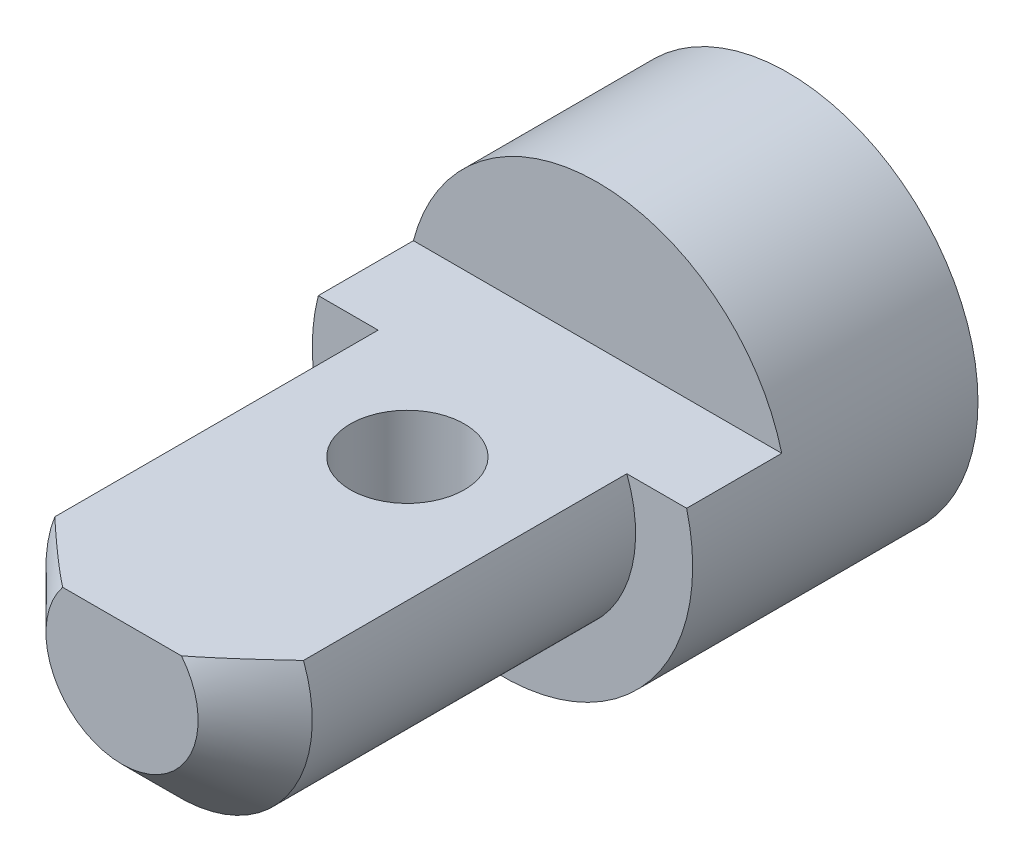
SolidWorks part; units mm, degrees
ref_plane "Front Plane" through (0, 0, 0) normal (0, 0, 1) x (1, 0, 0)
ref_plane "Top Plane" through (0, 0, 0) normal (0, 1, 0) x (1, 0, 0)
ref_plane "Right Plane" through (0, 0, 0) normal (1, 0, 0) x (0, 0, -1)
sketch "Sketch1" plane through (0, 0, 0) normal (0, 0, 1) x (1, 0, 0)
  line L0 (-19.3649, 5) -> (19.3649, 5)
  circle A0 centre (0, 0) radius 20
  circle A1 centre (0, 0) radius 14
  dimension "D1" = 40
  dimension "D2" = 28
  dimension "D3" = 5
extrude "Boss-Extrude1" add sketch "Sketch1" against normal blind 20 contours L0 A1 | L0 A1 | A1 L0 A0 | A1 L0 A0 region at (0, 19.5847, 0) region at (-16.2208, 4.5283, 0) region at (0, 8.7223, 0) region at (0, -3.3512, 0)
extrude "Boss-Extrude2" add sketch "Sketch1<4>" along normal blind 10 contours A1 L0 A0 region at (-16.2208, 4.5283, 0)
sketch "Sketch1<4>" plane through (0, 0, 0) normal (0, 0, 1) x (1, 0, 0) same geometry as "Sketch1"
extrude "Boss-Extrude3" add sketch "Sketch1<5>" along normal blind 50 contours L0 A1 region at (0, -3.3512, 0)
sketch "Sketch1<5>" plane through (0, 0, 0) normal (0, 0, 1) x (1, 0, 0) same geometry as "Sketch1"
chamfer "Chamfer3" distance 6 angle 45 1 edges at (0, -14, 50)
sketch "Sketch3" plane through (0, 5, 0) normal (0, 1, 0) x (1, 0, 0)
  line L0 (-6.245, -50) -> (6.245, -50) construction
  circle A0 centre (0, -20) radius 6
  point P2 (0, 0)
  dimension "D1" = 12
  dimension "D2" = 30
extrude "Cut-Extrude1" cut sketch "Sketch3" against normal blind 50
